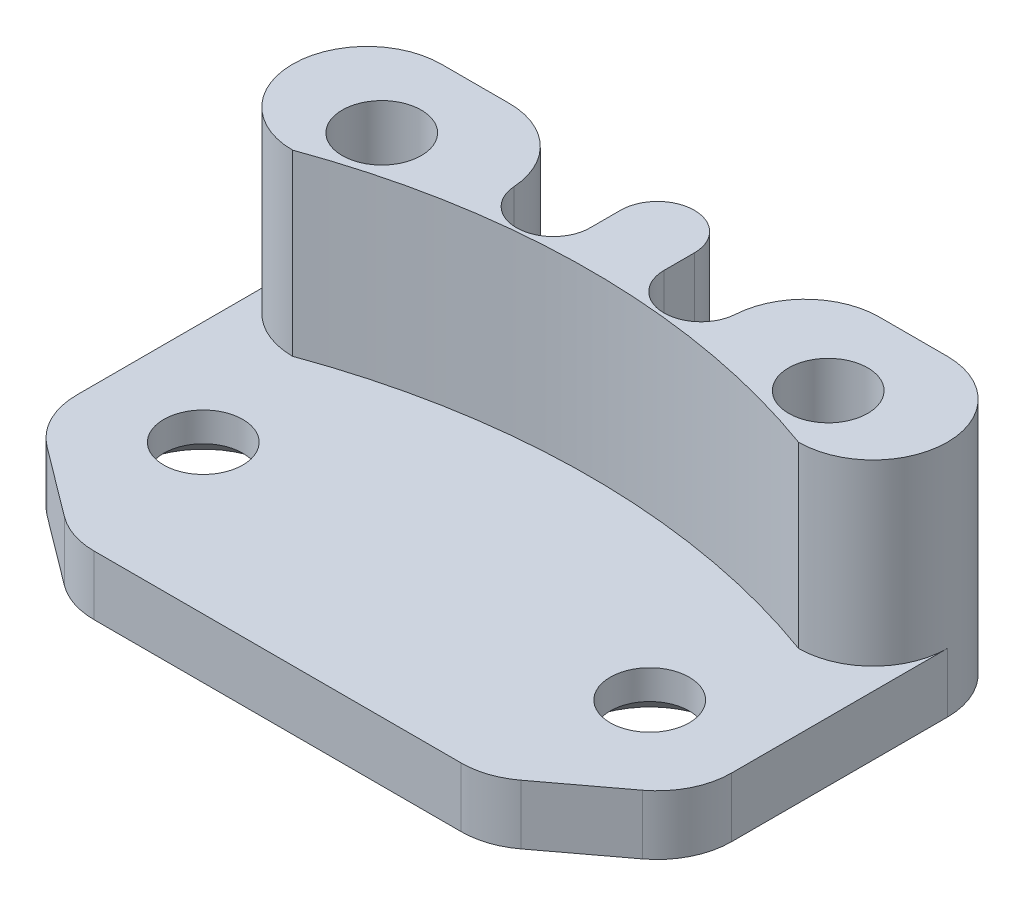
SolidWorks part; units mm, degrees
material "1060 Alloy"
ref_plane "Front Plane" through (0, 0, 0) normal (0, 0, 1) x (1, 0, 0)
ref_plane "Top Plane" through (0, 0, 0) normal (0, 1, 0) x (1, 0, 0)
ref_plane "Right Plane" through (0, 0, 0) normal (1, 0, 0) x (0, 0, -1)
sketch "Sketch1" plane through (0, 0, 0) normal (0, 1, 0) x (1, 0, 0)
  line L0 (0, 0) -> (-23.8125, 0) construction
  line L1 (0, 0) -> (23.8125, 0) construction
  line L2 (-34.925, -15.875) -> (-34.925, 28.575)
  line L3 (-34.925, -15.875) -> (34.925, -15.875)
  line L4 (-34.925, 28.575) -> (34.925, 28.575)
  line L5 (34.925, 28.575) -> (34.925, -15.875)
  line L6 (-7.9375, 7.9248) -> (-34.925, 7.9248) construction
  line L7 (7.9375, 7.9248) -> (34.925, 7.9248) construction
  line L8 (-11.811, 28.575) -> (-11.811, 17.4625)
  line L9 (-11.811, 17.4625) -> (-3.937, 17.4625)
  line L10 (-3.937, 17.4625) -> (-3.937, 28.575)
  line L11 (3.937, 28.575) -> (3.937, 17.4625)
  line L12 (3.937, 17.4625) -> (11.811, 17.4625)
  line L13 (11.811, 17.4625) -> (11.811, 28.575)
  line L14 (-34.925, -6.35) -> (-22.225, -15.875)
  line L15 (34.925, -6.35) -> (22.225, -15.875)
  line L16 (11.811, 17.4625) -> (34.925, 17.4625) construction
  line L17 (-11.811, 17.4625) -> (-34.925, 17.4625) construction
  circle A0 centre (0, 0) radius 14.2875
  circle A1 centre (-23.8125, 0) radius 5.2754
  circle A2 centre (23.8125, 0) radius 5.2754
  circle A3 centre (-23.8252, 19.05) radius 4.1672
  circle A4 centre (23.7998, 19.05) radius 4.1672
  circle A6 centre (-7.9375, 7.9248) radius 3.3655
  circle A7 centre (7.9375, 7.9248) radius 3.3655
  circle A8 centre (0, 0) radius 12.7
  dimension "D1" = 28.575
  dimension "D2" = 10.5508
  dimension "D4" = 34.925
  dimension "D7" = 11.0998
  dimension "D9" = 8.3344
  dimension "D10" = 8.3344
  dimension "D12" = 25.4
  dimension "D14" = 15.875
  dimension "D15" = 6.731
  dimension "D3" = 47.625
  dimension "D5" = 44.45
  dimension "D6" = 15.875
  dimension "D8" = 19.05
  dimension "D11" = 47.625
  dimension "D13" = 34.925
  dimension "D16" = 23.7998
  dimension "D17" = 7.874
  dimension "D18" = 7.874
  dimension "D19" = 44.45
  dimension "D20" = 9.525
  dimension "D21" = 11.1125
  dimension "D22" = 7.874
sketch "Sketch2" plane through (0, 0, 0) normal (0, 1, 0) x (1, 0, 0)
  line L0 (-11.811, 17.4625) -> (-3.937, 17.4625) construction
  line L1 (-11.811, 28.575) -> (-11.811, 17.4625) construction
  line L2 (-3.937, 17.4625) -> (-3.937, 28.575) construction
  line L3 (11.811, 17.4625) -> (11.811, 28.575) construction
  line L4 (3.937, 17.4625) -> (11.811, 17.4625) construction
  line L5 (3.937, 28.575) -> (3.937, 17.4625) construction
  line L6 (-34.925, 28.575) -> (34.925, 28.575) construction
  line L7 (34.925, 28.575) -> (34.925, -15.875) construction
  line L8 (34.925, -6.35) -> (22.225, -15.875) construction
  line L9 (-34.925, -15.875) -> (34.925, -15.875) construction
  line L10 (-34.925, -6.35) -> (-22.225, -15.875) construction
  line L11 (-34.925, -15.875) -> (-34.925, 28.575) construction
  line L12 (-11.811, 17.4625) -> (-3.937, 17.4625)
  line L13 (-11.811, 28.575) -> (-11.811, 17.4625)
  line L14 (-3.937, 17.4625) -> (-3.937, 28.575)
  line L15 (11.811, 17.4625) -> (11.811, 28.575)
  line L16 (3.937, 17.4625) -> (11.811, 17.4625)
  line L17 (3.937, 28.575) -> (3.937, 17.4625)
  line L18 (-34.925, 28.575) -> (-11.811, 28.575)
  line L19 (34.925, 28.575) -> (34.925, -6.35)
  line L20 (34.925, -6.35) -> (22.225, -15.875)
  line L21 (-22.225, -15.875) -> (22.225, -15.875)
  line L22 (-34.925, -6.35) -> (-22.225, -15.875)
  line L23 (-34.925, -6.35) -> (-34.925, 28.575)
  line L24 (-3.937, 28.575) -> (3.937, 28.575)
  line L25 (11.811, 28.575) -> (34.925, 28.575)
extrude "Boss-Extrude1" add sketch "Sketch2" along normal blind 25.4
fillet "Fillet1" radius 3.937 6 edges at (11.811, 12.7, -17.4625) (3.937, 12.7, -17.4625) (3.937, 12.7, -28.575) (-3.937, 12.7, -28.575) (-3.937, 12.7, -17.4625) (-11.811, 12.7, -17.4625)
fillet "Fillet2" radius 7.9375 8 edges at (34.925, 12.7, 6.35) (22.225, 12.7, 15.875) (-22.225, 12.7, 15.875) (-34.925, 12.7, 6.35) (34.925, 12.7, -28.575) (11.811, 12.7, -28.575) (-11.811, 12.7, -28.575) (-34.925, 12.7, -28.575)
hole_wizard "5/16 Clearance Hole1" positions "Sketch3" profile "Sketch4" hole size "5/16" standard "ANSI Inch" end condition through all
sketch "Sketch3" plane through (0, 25.4, 0) normal (0, 1, 0) x (1, 0, 0)
  point P0 (-23.8252, 19.05)
  point P3 (23.7998, 19.05)
sketch "Sketch4" plane through (-23.8252, 25.4, -19.05) normal (1, 0, 0) x (0, 0, 1)
  line L0 (0, 0) -> (0, 25.4)
  line L1 (0, 25.4) -> (4.2164, 25.4)
  line L2 (4.2164, 25.4) -> (4.2164, 0)
  line L5 (4.2164, 0) -> (0, 0)
  line L11 (0, -6.35) -> (0, 107.95) construction
  dimension "Thru Hole Dia." = 8.4328
  dimension "Thru Hole Depth" = 25.4
hole_wizard "CSK for 5/16 Flat Head Machine Screw (100)1" positions "Sketch7" profile "Sketch6" countersink size "5/16" standard "ANSI Inch" end condition through all
sketch "Sketch7" plane through (0, 0, 0) normal (0, -1, 0) x (-1, 0, 0)
  point P0 (-23.8125, 0)
  point P3 (23.8125, 0)
sketch "Sketch6" plane through (23.8125, 0, 0) normal (1, 0, 0) x (0, 0, -1)
  line L0 (0, 0) -> (0, 25.4)
  line L1 (0, 25.4) -> (4.2164, 25.4)
  line L2 (4.2164, 25.4) -> (4.2164, 3.2289)
  line L3 (4.2164, 3.2289) -> (8.0645, 0)
  line L5 (8.0645, 0) -> (0, 0)
  line L6 (-4.2164, 3.2289) -> (-8.0645, 0) construction
  line L11 (0, -6.35) -> (0, 107.95) construction
  dimension "Thru Hole Dia." = 8.4328
  dimension "Thru Hole Depth" = 25.4
  dimension "Near C'Sink Dia." = 16.129
  dimension "Near C'Sink Angle" = 100
sketch "Sketch8" plane through (0, 25.4, 0) normal (0, 1, 0) x (1, 0, 0)
  line L2 (-34.925, 20.6375) -> (-19.05, 20.6375) construction
  line L3 (-34.925, 20.6375) -> (-36.624, 20.6375) construction
  line L4 (24.3417, -14.2875) -> (31.75, -8.7312) construction
  line L5 (34.925, 20.6375) -> (19.05, 20.6375) construction
  line L6 (-19.5792, -15.875) -> (19.5792, -15.875) construction
  line L7 (-31.75, -8.7312) -> (-24.3417, -14.2875) construction
  line L10 (24.3417, -14.2875) -> (31.75, -8.7312)
  line L11 (-19.5792, -15.875) -> (19.5792, -15.875)
  line L12 (-31.75, -8.7312) -> (-24.3417, -14.2875)
  line L16 (34.925, 20.6375) -> (36.1263, 20.6375) construction
  line L17 (36.1263, 20.6375) -> (36.1263, -2.3813) construction
  line L18 (36.1263, -2.3813) -> (34.925, -2.3813) construction
  line L19 (-36.624, 20.6375) -> (-36.624, -2.3812) construction
  line L20 (-36.624, -2.3812) -> (-34.925, -2.3812) construction
  line L21 (-34.925, 20.6375) -> (-34.925, -2.3812) construction
  line L22 (34.925, 20.6375) -> (34.925, -2.3813) construction
  line L23 (-7.874, 17.4625) -> (7.874, 17.4625) construction
  line L24 (-34.925, 20.6375) -> (-34.925, -2.3812)
  line L25 (34.925, 20.6375) -> (34.925, -2.3813)
  circle A1 centre (-26.9875, 20.6375) radius 7.9375 construction
  circle A3 centre (26.9875, 20.6375) radius 7.9375 construction
  arc A5 (34.925, 20.6375) -> (26.9875, 28.575) centre (26.9875, 20.6375) ccw construction
  arc A6 (-26.9875, 28.575) -> (-34.925, 20.6375) centre (-26.9875, 20.6375) ccw construction
  arc A7 (-26.9875, 12.7) -> (26.9875, 12.7) centre (0, -61.3833) cw
  arc A8 (-34.925, 20.6375) -> (-26.9875, 12.7) centre (-26.9875, 20.6375) ccw
  arc A9 (34.925, 20.6375) -> (26.9875, 12.7) centre (26.9875, 20.6375) cw
  arc A10 (31.75, -8.7312) -> (34.925, -2.3813) centre (26.9875, -2.3813) ccw construction
  arc A11 (19.5792, -15.875) -> (24.3417, -14.2875) centre (19.5792, -7.9375) ccw construction
  arc A12 (-24.3417, -14.2875) -> (-19.5792, -15.875) centre (-19.5792, -7.9375) ccw construction
  arc A13 (-34.925, -2.3812) -> (-31.75, -8.7312) centre (-26.9875, -2.3812) ccw construction
  arc A14 (31.75, -8.7312) -> (34.925, -2.3813) centre (26.9875, -2.3813) ccw
  arc A15 (19.5792, -15.875) -> (24.3417, -14.2875) centre (19.5792, -7.9375) ccw
  arc A16 (-24.3417, -14.2875) -> (-19.5792, -15.875) centre (-19.5792, -7.9375) ccw
  arc A17 (-34.925, -2.3812) -> (-31.75, -8.7312) centre (-26.9875, -2.3812) ccw
  arc A18 (7.874, 17.4625) -> (11.8029, 21.1469) centre (7.874, 21.3995) ccw construction
  dimension "D1" = 23.0187
  dimension "D2" = 1.2013
  dimension "D3" = 1.699
extrude "Cut-Extrude2" cut sketch "Sketch8" against normal blind 19.05
